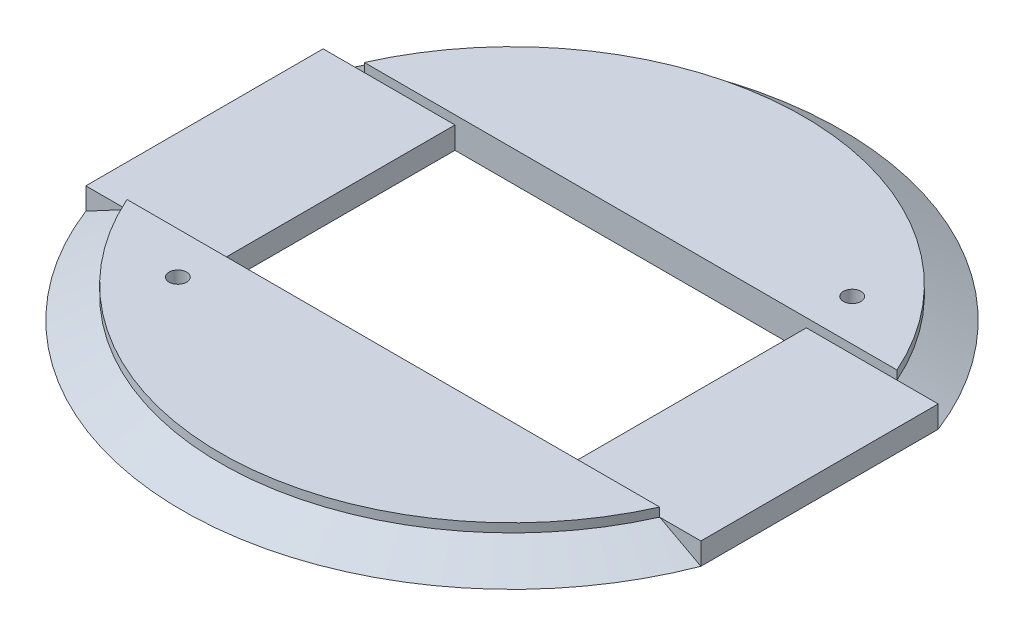
SolidWorks part; units mm, degrees
ref_plane "Front Plane" through (0, 0, 0) normal (0, 0, 1) x (1, 0, 0)
ref_plane "Top Plane" through (0, 0, 0) normal (0, 1, 0) x (1, 0, 0)
ref_plane "Right Plane" through (0, 0, 0) normal (1, 0, 0) x (0, 0, -1)
sketch "Sketch3" plane through (0, 0, 0) normal (0, 0, 1) x (1, 0, 0)
  line L0 (0, 0) -> (37.5, 0)
  line L1 (0, 0) -> (0, 2.5)
  line L2 (37.5, 0) -> (33.1709, 2.5)
  line L3 (0, 2.5) -> (33.1709, 2.5)
  point P3 (0, 0)
revolve "Revolve1" add sketch "Sketch3" angle 360 about L1
sketch "Sketch7" plane through (0, 2.5, 0) normal (0, 1, 0) x (1, 0, 0)
  circle A0 centre (0, 0) radius 33.1709
extrude "Boss-Extrude2" add sketch "Sketch7" along normal blind 1
sketch "Sketch13" plane through (0, 0, 0) normal (0, -1, 0) x (1, 0, 0)
  line L0 (-37.5, -13.5) -> (37.5, -13.5) construction
  line L1 (-37.5, -13.5) -> (-37.5, 13.5)
  line L2 (37.5, -13.5) -> (37.5, 13.5)
  line L3 (-37.5, 13.5) -> (37.5, 13.5)
  line L4 (-37.5, -13.5) -> (37.5, 13.5) construction
  line L5 (37.5, -13.5) -> (-37.5, 13.5) construction
  line L7 (-37.5, -13.5) -> (37.5, -13.5)
  point P1 (0, 0)
extrude "Cut-Extrude2" cut sketch "Sketch13" against normal through all
sketch "Sketch18" plane through (0, 0, 0) normal (0, 1, 0) x (1, 0, 0)
  line L0 (-34.9857, 13.5) -> (34.9857, 13.5) construction
  line L1 (34.9857, -13.5) -> (19.9888, -13.5)
  line L2 (34.9857, -13.5) -> (34.9857, 13.5)
  line L3 (34.9857, 13.5) -> (19.9888, 13.5)
  line L4 (19.9888, -13.5) -> (19.9888, 13.5)
  line L6 (-34.9857, -13.5) -> (-19.9873, -13.5)
  line L7 (-34.9857, -13.5) -> (-34.9857, 13.5)
  line L8 (-34.9857, 13.5) -> (-19.9873, 13.5)
  line L9 (-19.9873, -13.5) -> (-19.9873, 13.5)
extrude "Boss-Extrude4" add sketch "Sketch18" along normal blind 2.5 contours L2 L3 L4 L1
extrude "Boss-Extrude5" add sketch "Sketch18<3>" along normal blind 2.5
sketch "Sketch18<3>" plane through (0, 0, 0) normal (0, 1, 0) x (1, 0, 0) same geometry as "Sketch18"
sketch "Sketch20" plane through (0, 3.5, 0) normal (0, 1, 0) x (1, 0, 0)
  circle A0 centre (-19.7571, -18.2566) radius 0.9993
  circle A1 centre (20.4975, 18.2004) radius 1.0004
extrude "Cut-Extrude3" cut sketch "Sketch20" against normal through all
